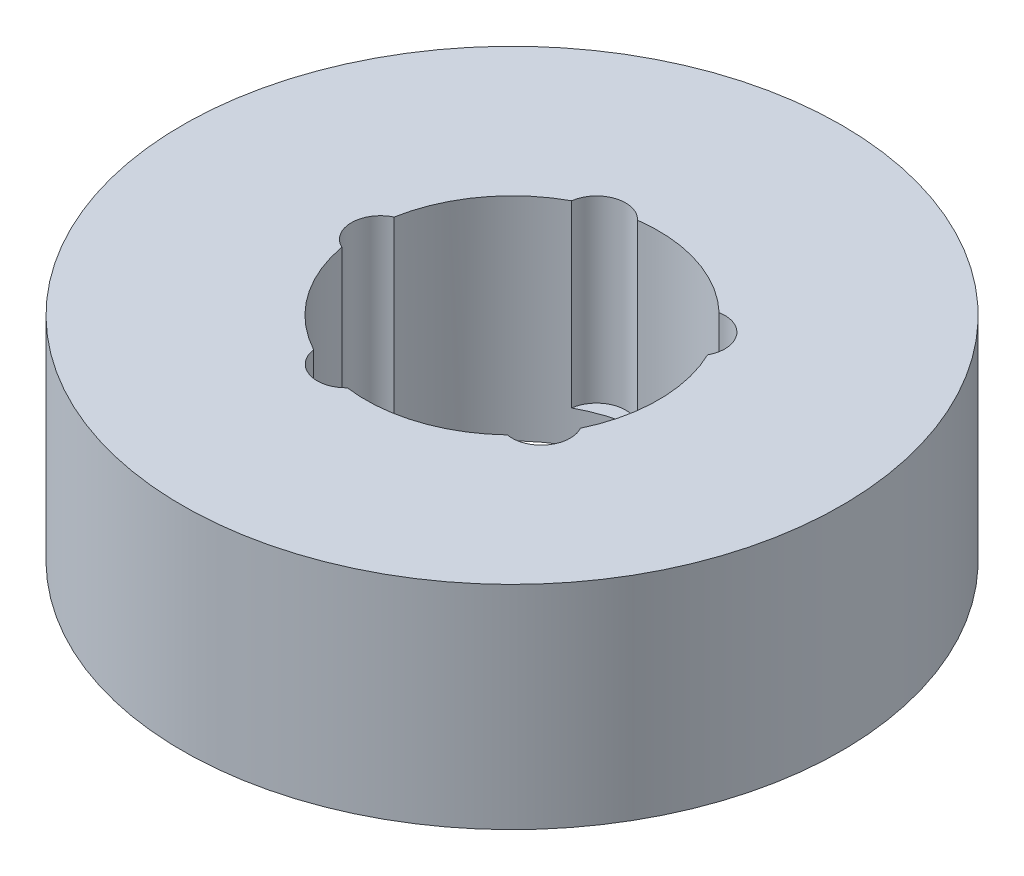
SolidWorks part; units mm, degrees
ref_plane "Front Plane" through (0, 0, 0) normal (0, 0, 1) x (1, 0, 0)
ref_plane "Top Plane" through (0, 0, 0) normal (0, 1, 0) x (1, 0, 0)
ref_plane "Right Plane" through (0, 0, 0) normal (1, 0, 0) x (0, 0, -1)
sketch "Sketch1" plane through (0, 0, 0) normal (0, 1, 0) x (1, 0, 0)
  circle A0 centre (0, 0) radius 45
  dimension "FLANGE_OD" = 90
extrude "Boss-Extrude1" add sketch "Sketch1" along normal blind 29
sketch "Sketch2" plane through (0, 0, 0) normal (0, 1, 0) x (1, 0, 0)
  circle A0 centre (0, 0) radius 20
  dimension "BORE_D" = 40
extrude "Cut-Extrude1" cut sketch "Sketch2" along normal through all
sketch "Sketch3" plane through (0, 29, 0) normal (0, 1, 0) x (1, 0, 0)
  circle A0 centre (0, 0) radius 17.9712 construction
  circle A1 centre (-17.9712, 0) radius 3.9608
  dimension "BOLT_D" = 7.9216
  dimension "BOLT_PCD" = 35.9424
extrude "Cut-Extrude2" cut sketch "Sketch3" against normal blind 24.5003
pattern_circular "CirPattern1" count 5 over 360 about axis through (0, 0, 0) along (0, 1, 0) of "Cut-Extrude2"
